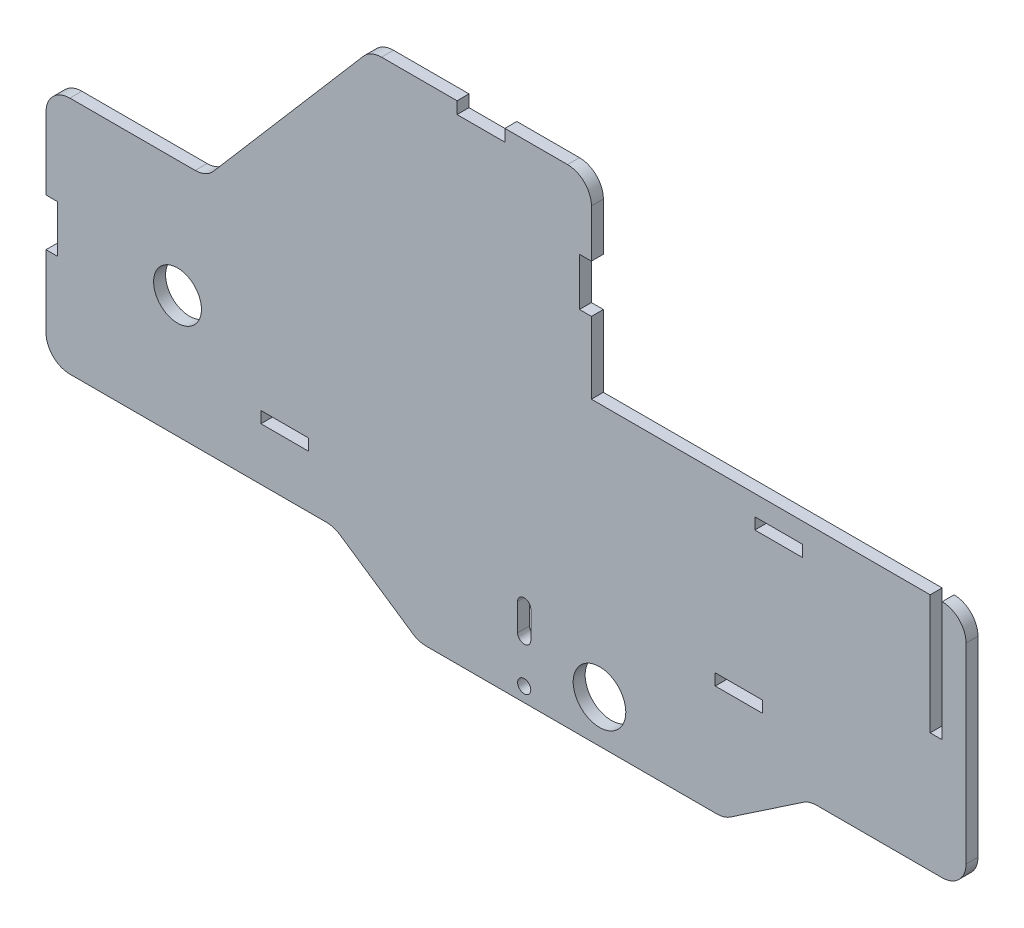
SolidWorks part; units mm, degrees
ref_plane "Front Plane" through (0, 0, 0) normal (0, 0, 1) x (1, 0, 0)
ref_plane "Top Plane" through (0, 0, 0) normal (0, 1, 0) x (1, 0, 0)
ref_plane "Right Plane" through (0, 0, 0) normal (1, 0, 0) x (0, 0, -1)
sketch "Sketch1" plane through (0, 0, 0) normal (0, 0, 1) x (1, 0, 0)
  line L0 (62.1239, 6.35) -> (131.9663, 6.35)
  line L1 (201.8088, 12.7) -> (201.8088, 76.2)
  line L2 (201.8088, 76.2) -> (102.3141, 76.2)
  line L3 (102.3141, 76.2) -> (102.3141, 127)
  line L4 (102.3141, 127) -> (43.6394, 127)
  line L5 (43.6394, 127) -> (0, 76.2)
  line L6 (0, 76.2) -> (-42.5392, 76.2)
  line L7 (-42.5392, 76.2) -> (-42.5392, 12.7)
  line L9 (-42.5392, 12.7) -> (46.6174, 12.7)
  line L10 (46.6174, 12.7) -> (62.1239, 6.35)
  line L11 (201.8088, 12.7) -> (147.4729, 12.7)
  line L12 (147.4729, 12.7) -> (131.9663, 6.35)
  dimension "D1" = 244.348
  dimension "D2" = 6.35
  dimension "D3" = 50.8
  dimension "D4" = 63.5
  dimension "D5" = 99.4947
  dimension "D6" = 16.7564
  dimension "D7" = 16.7564
extrude "Main Side" add sketch "Sketch1" along normal blind 3.175
sketch "Sketch2" plane through (0, 0, 3.175) normal (0, 0, 1) x (1, 0, 0)
  line L0 (-39.4912, 76.2) -> (-39.4912, 12.7) construction
  line L15 (0, 76.2) -> (-42.5392, 76.2) construction
  line L16 (-42.5392, 76.2) -> (-42.5392, 12.7) construction
  line L26 (-39.4912, 18.5744) -> (201.8088, 18.5744) construction
  line L27 (201.8088, 12.7) -> (201.8088, 76.2) construction
  line L28 (81.1588, 18.5744) -> (81.1588, 127) construction
  line L29 (102.3141, 127) -> (43.6394, 127) construction
  line L30 (81.1588, 36.7006) -> (201.8088, 36.7006) construction
  line L41 (62.1239, 6.35) -> (131.9663, 6.35) construction
  line L42 (135.1973, 29.718) -> (147.7703, 29.718)
  line L43 (135.1973, 29.718) -> (135.1973, 26.67)
  line L44 (135.1973, 26.67) -> (147.7703, 26.67)
  line L45 (147.7703, 29.718) -> (147.7703, 26.67)
  line L46 (14.5473, 29.718) -> (14.5473, 26.67)
  line L47 (27.1203, 26.67) -> (14.5473, 26.67)
  line L48 (27.1203, 29.718) -> (27.1203, 26.67)
  line L49 (27.1203, 29.718) -> (14.5473, 29.718)
  line L51 (-42.5392, 12.7) -> (46.6174, 12.7) construction
  point P20 (141.4838, 29.718)
  point P21 (141.4838, 36.7006)
  dimension "D1" = 12.573
  dimension "D2" = 3.048
  dimension "D3" = 20.32
  dimension "D4" = 3.048
extrude "Bottom Plate Holes" cut sketch "Sketch2" against normal through all
sketch "Sketch3" plane through (0, 0, 3.175) normal (0, 0, 1) x (1, 0, 0)
  line L1 (145.7115, 70.866) -> (158.4115, 70.866)
  line L2 (145.7115, 70.866) -> (145.7115, 67.818)
  line L3 (145.7115, 67.818) -> (158.4115, 67.818)
  line L4 (158.4115, 70.866) -> (158.4115, 67.818)
  line L6 (147.7703, 29.718) -> (135.1973, 29.718) construction
  line L7 (201.8088, 76.2) -> (102.3141, 76.2) construction
  point P8 (152.0615, 76.2)
  point P9 (152.0615, 70.866)
  dimension "D1" = 12.7
  dimension "D2" = 3.048
  dimension "D3" = 38.1
extrude "Cut-Extrude1" cut sketch "Sketch3" against normal through all
sketch "Sketch4" plane through (0, 0, 3.175) normal (0, 0, 1) x (1, 0, 0)
  line L0 (-42.5392, 76.2) -> (-42.5392, 12.7) construction
  line L1 (-42.5392, 50.7365) -> (-39.4912, 50.7365)
  line L2 (-42.5392, 50.7365) -> (-42.5392, 38.1635)
  line L3 (-42.5392, 38.1635) -> (-39.4912, 38.1635)
  line L4 (-39.4912, 50.7365) -> (-39.4912, 38.1635)
  point P6 (-42.5392, 44.45)
  point P7 (-42.5392, 44.45)
  dimension "D1" = 3.048
  dimension "D2" = 12.573
extrude "Cut-Extrude2" cut sketch "Sketch4" against normal through all
sketch "Sketch5" plane through (0, 0, 3.175) normal (0, 0, 1) x (1, 0, 0)
  line L0 (201.8088, 76.2) -> (102.3141, 76.2) construction
  line L1 (192.2838, 76.2) -> (195.4588, 76.2)
  line L2 (192.2838, 76.2) -> (192.2838, 44.45)
  line L3 (192.2838, 44.45) -> (195.4588, 44.45)
  line L4 (195.4588, 76.2) -> (195.4588, 44.45)
  line L5 (201.8088, 12.7) -> (201.8088, 76.2) construction
  dimension "D1" = 3.175
  dimension "D2" = 31.75
  dimension "D3" = 6.35
extrude "Cut-Extrude3" cut sketch "Sketch5" against normal through all
sketch "Sketch6" plane through (0, 0, 3.175) normal (0, 0, 1) x (1, 0, 0)
  line L0 (-42.5392, 76.2) -> (-42.5392, 50.7365) construction
  line L1 (0, 76.2) -> (-42.5392, 76.2) construction
  circle A0 centre (-7.6142, 45.085) radius 6.35
  dimension "D2" = 31.115
  dimension "D3" = 12.7
  dimension "D1" = 34.925
extrude "Cut-Extrude4" cut sketch "Sketch6" against normal through all
sketch "Sketch7" plane through (0, 0, 3.175) normal (0, 0, 1) x (1, 0, 0)
  line L0 (102.3141, 127) -> (43.6394, 127) construction
  line L1 (66.6267, 127) -> (79.3267, 127)
  line L2 (66.6267, 127) -> (66.6267, 123.825)
  line L3 (66.6267, 123.825) -> (79.3267, 123.825)
  line L4 (79.3267, 127) -> (79.3267, 123.825)
  point P6 (72.9767, 127)
  point P7 (72.9767, 127)
  dimension "D1" = 3.175
  dimension "D2" = 12.7
extrude "Cut-Extrude5" cut sketch "Sketch7" against normal through all
sketch "Sketch8" plane through (0, 0, 3.175) normal (0, 0, 1) x (1, 0, 0)
  line L0 (102.3141, 76.2) -> (102.3141, 127) construction
  line L1 (99.1391, 107.95) -> (102.3141, 107.95)
  line L2 (99.1391, 107.95) -> (99.1391, 95.25)
  line L3 (99.1391, 95.25) -> (102.3141, 95.25)
  line L4 (102.3141, 107.95) -> (102.3141, 95.25)
  point P6 (102.3141, 101.6)
  point P7 (102.3141, 101.6)
  dimension "D1" = 3.175
  dimension "D2" = 12.7
extrude "Cut-Extrude6" cut sketch "Sketch8" against normal through all
sketch "Sketch13" plane through (0, 0, 3.175) normal (0, 0, 1) x (1, 0, 0)
  line L1 (-42.5392, 12.7) -> (46.6174, 12.7) construction
  line L4 (147.4729, 12.7) -> (201.8088, 12.7) construction
  line L5 (33.9174, 12.7) -> (56.4826, -2.54)
  line L6 (56.4826, -2.54) -> (137.6077, -2.54)
  line L7 (137.6077, -2.54) -> (160.1729, 12.7)
  line L8 (33.9174, 12.7) -> (46.6174, 12.7)
  line L9 (46.6174, 12.7) -> (62.1239, 6.35)
  line L10 (62.1239, 6.35) -> (131.9663, 6.35)
  line L11 (131.9663, 6.35) -> (147.4729, 12.7)
  line L12 (147.4729, 12.7) -> (160.1729, 12.7)
  dimension "D1" = 8.89
  dimension "D2" = 12.7
  dimension "D3" = 12.7
  dimension "D4" = 145.966
  dimension "D5" = 145.966
extrude "Boss-Extrude2" add sketch "Sketch13" against normal blind 3.175
sketch "Sketch10" plane through (0, 0, 3.175) normal (0, 0, 1) x (1, 0, 0)
  line L0 (84.4608, 19.8624) -> (84.4608, 12.6776) construction
  line L1 (86.2108, 19.8624) -> (86.2108, 12.6776)
  line L2 (82.7108, 19.8624) -> (82.7108, 12.6776)
  line L3 (84.4608, 16.27) -> (84.4608, 1.27) construction
  line L4 (-42.5392, 38.1635) -> (-42.5392, 12.7) construction
  line L6 (56.4826, -2.54) -> (137.6077, -2.54) construction
  circle A0 centre (84.4608, 1.27) radius 1.75
  arc A1 (86.2108, 19.8624) -> (82.7108, 19.8624) centre (84.4608, 19.8624) ccw
  arc A2 (82.7108, 12.6776) -> (86.2108, 12.6776) centre (84.4608, 12.6776) ccw
  circle A3 centre (104.4608, 8.77) radius 6.985
  point P4 (84.4608, 16.27)
  point P13 (84.4608, 8.77)
  dimension "D2" = 3.5
  dimension "D4" = 13.97
  dimension "D6" = 7.1848
  dimension "D1" = 15
  dimension "D3" = 3.5
  dimension "D5" = 20
  dimension "D7" = 127
  dimension "D8" = 3.81
extrude "Cut-Extrude7" cut sketch "Sketch10" against normal through all
fillet "Fillet1" radius 6.35 11 edges at (102.3141, 127, 1.5875) (43.6394, 127, 1.5875) (0, 76.2, 1.5875) (201.8088, 12.7, 1.5875) (-42.5392, 12.7, 1.5875) (201.8088, 76.2, 1.5875) (-42.5392, 76.2, 1.5875) (160.1729, 12.7, 1.5875) (137.6077, -2.54, 1.5875) (56.4826, -2.54, 1.5875) (33.9174, 12.7, 1.5875)
